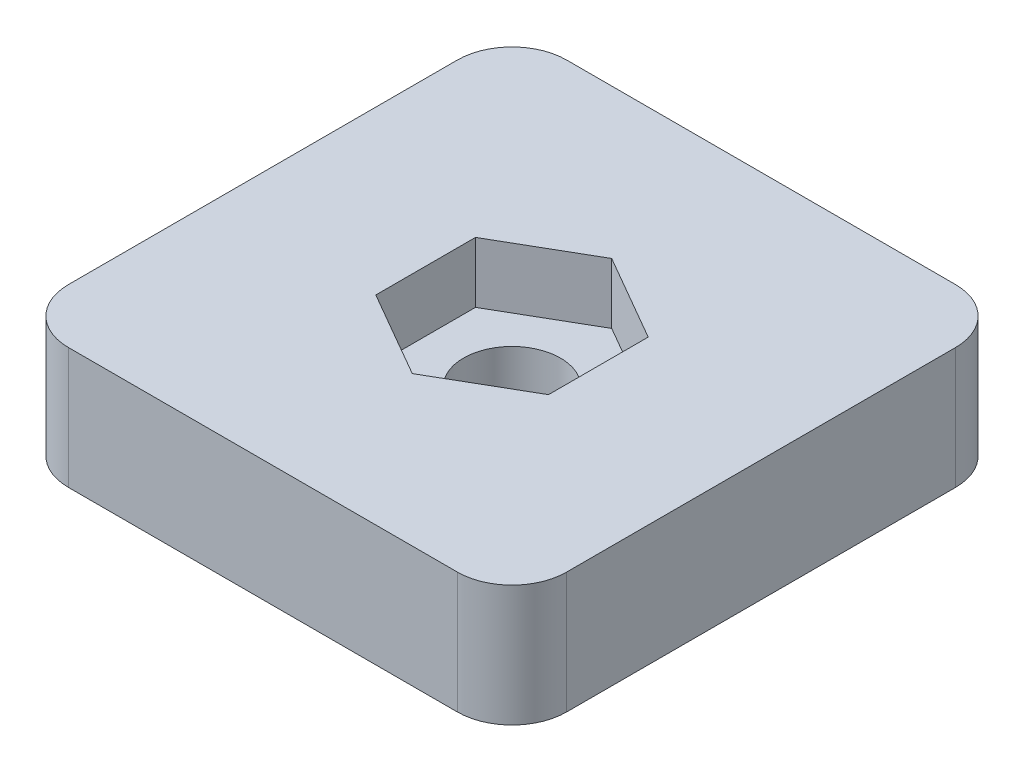
SolidWorks part; units mm, degrees
ref_plane "前视基准面" through (0, 0, 0) normal (0, 0, 1) x (1, 0, 0)
ref_plane "上视基准面" through (0, 0, 0) normal (0, 1, 0) x (1, 0, 0)
ref_plane "右视基准面" through (0, 0, 0) normal (1, 0, 0) x (0, 0, -1)
sketch "草图1" plane through (0, 0, 0) normal (0, 1, 0) x (1, 0, 0)
  line L0 (-8.22, -6.42) -> (-8.22, 6.42)
  line L1 (-6.42, -9.42) -> (6.42, -9.42)
  line L2 (-9.42, -6.42) -> (-9.42, 6.42)
  line L3 (-6.42, 9.42) -> (6.42, 9.42)
  line L4 (9.42, -6.42) -> (9.42, 6.42)
  line L5 (0, 9.42) -> (0, -9.42) construction
  line L6 (-9.42, 0) -> (9.42, 0) construction
  line L7 (-6.42, 8.22) -> (6.42, 8.22)
  line L8 (8.22, -6.42) -> (8.22, 6.42)
  line L9 (-6.42, -8.22) -> (6.42, -8.22)
  line L11 (0, -3.2909) -> (2.85, -1.6454)
  line L12 (2.85, -1.6454) -> (2.85, 1.6454)
  line L13 (2.85, 1.6454) -> (0, 3.2909)
  line L14 (0, 3.2909) -> (-2.85, 1.6454)
  line L15 (-2.85, 1.6454) -> (-2.85, -1.6454)
  line L16 (-2.85, -1.6454) -> (0, -3.2909)
  arc A0 (-6.42, -9.42) -> (-9.42, -6.42) centre (-6.42, -6.42) cw
  arc A1 (6.42, -9.42) -> (9.42, -6.42) centre (6.42, -6.42) ccw
  arc A2 (9.42, 6.42) -> (6.42, 9.42) centre (6.42, 6.42) ccw
  arc A3 (-6.42, 9.42) -> (-9.42, 6.42) centre (-6.42, 6.42) ccw
  arc A4 (-6.42, 8.22) -> (-8.22, 6.42) centre (-6.42, 6.42) ccw
  arc A5 (8.22, 6.42) -> (6.42, 8.22) centre (6.42, 6.42) ccw
  arc A6 (6.42, -8.22) -> (8.22, -6.42) centre (6.42, -6.42) ccw
  arc A7 (-6.42, -8.22) -> (-8.22, -6.42) centre (-6.42, -6.42) cw
  circle A8 centre (0, 0) radius 2.85 construction
  circle A9 centre (0, 0) radius 1.6
  point P0 (0, 0)
  dimension "D3" = 3
  dimension "D5" = 5.7
  dimension "D1" = 18.84
  dimension "D2" = 18.84
  dimension "D4" = 1.2
extrude "凸台-拉伸5" add sketch "草图1" along normal blind 2 contours A7 L9 A6 L8 A5 L7 A4 L0 L16 L15 L14 L13 L12 L11 region at (-7.9875, 0, 0)
extrude "凸台-拉伸6" add sketch "草图1<7>" against normal blind 2 contours A7 L9 A6 L8 A5 L7 A4 L0 L16 L15 L14 L13 L12 L11 | L15 L16 L11 L12 L13 L14 A9 region at (-7.9875, 0, 0) region at (-1.3815, 0, 2.3928)
sketch "草图1<7>" plane through (0, 0, 0) normal (0, 1, 0) x (1, 0, 0) same geometry as "草图1"
